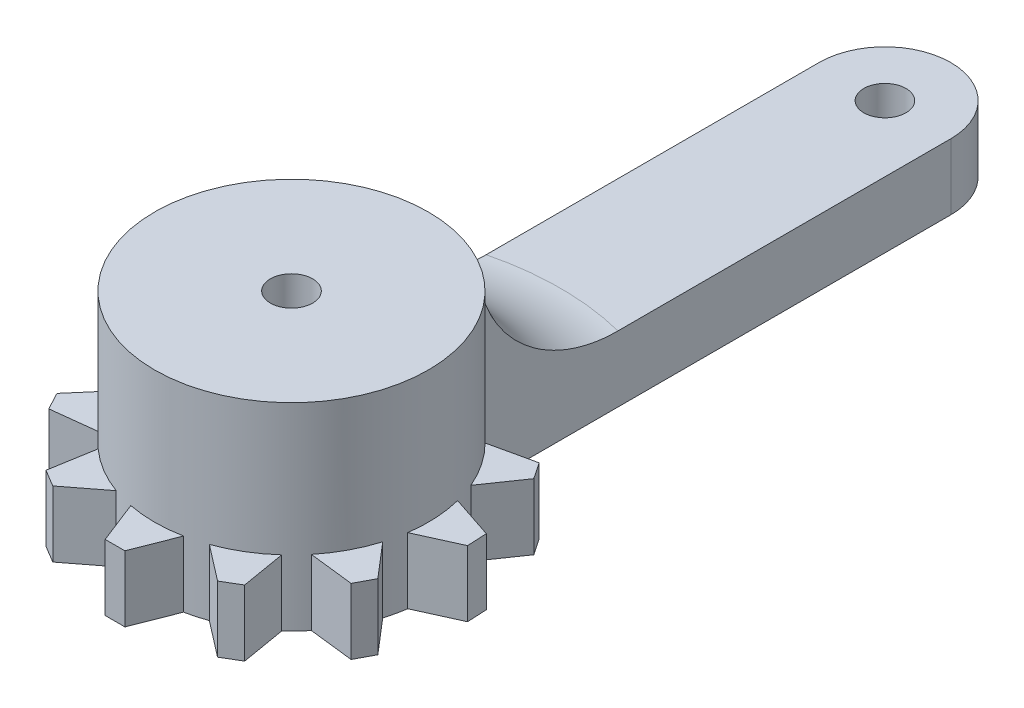
SolidWorks part; units mm, degrees
ref_plane "Front Plane" through (0, 0, 0) normal (0, 0, 1) x (1, 0, 0)
ref_plane "Top Plane" through (0, 0, 0) normal (0, 1, 0) x (1, 0, 0)
ref_plane "Right Plane" through (0, 0, 0) normal (1, 0, 0) x (0, 0, -1)
sketch "Sketch1" plane through (0, 0, 0) normal (0, 1, 0) x (1, 0, 0)
  line L0 (0, 0) -> (0, 45) construction
  line L1 (-5, 0) -> (-5, 45)
  line L2 (5, 0) -> (5, 45)
  circle A0 centre (0, 0) radius 10.38
  arc A1 (-5, 0) -> (5, 0) centre (0, 0) ccw
  arc A2 (5, 45) -> (-5, 45) centre (0, 45) ccw
  circle A3 centre (0, 45) radius 1.6
  circle A4 centre (0, 0) radius 1.6
  point P3 (0, 22.5)
  dimension "D1" = 20.76
  dimension "D4" = 3.2
  dimension "D5" = 3.2
  dimension "D2" = 10
  dimension "D3" = 45
extrude "Boss-Extrude1" add sketch "Sketch1" along normal blind 5 contours L2 A2 L1 A0 A3 | A1 L1 A0 L2 | A4 A0 L1 A1 L2 region at (0, 0, 5.2847) region at (0, 0, -3.1615) region at (0, 0, -29.1318)
sketch "Sketch2" plane through (0, 5, 0) normal (0, 1, 0) x (1, 0, 0)
  line L0 (0, -10.38) -> (0, -13.38) construction
  line L1 (-0.75, -13.38) -> (0.75, -13.38)
  line L2 (0.75, -13.38) -> (2, -10.1855)
  line L3 (-0.75, -13.38) -> (-2, -10.1855)
  arc A0 (-5, 9.0964) -> (5, 9.0964) centre (0, 0) ccw construction
  arc A1 (-2, -10.1855) -> (2, -10.1855) centre (0, 0) ccw
  point P14 (0, -13.38)
  dimension "D1" = 3
  dimension "D2" = 1.5
  dimension "D3" = 4
extrude "Boss-Extrude2" add sketch "Sketch2" against normal up to surface (5 mm away) up to face at (0, 0, -23.4291)
pattern_circular "CirPattern1" count 5 every 31 about axis through (0, 5, 0) along (0, -1, 0) of "Boss-Extrude2" other way count 5
sketch "Sketch3" plane through (0, 5, 0) normal (0, 1, 0) x (1, 0, 0)
  circle A0 centre (0, 0) radius 5.975
  circle A1 centre (0, 0) radius 1.6
  circle A2 centre (0, 0) radius 3.25
  arc A3 (7.3258, 7.3537) -> (5, 9.0964) centre (0, 0) ccw construction
  dimension "D1" = 11.95
  dimension "D2" = 6.5
  dimension "D3" = 3.2
extrude "Boss-Extrude3" [suppressed] add sketch "Sketch3" along normal blind 6.6 contours A0 A2
chamfer "Chamfer1" [suppressed] distance 1 angle 45
chamfer "Chamfer2" [suppressed] distance 0.5 angle 45
sketch "Sketch4" plane through (0, 5, 0) normal (0, 1, 0) x (1, 0, 0)
  circle A0 centre (0, 0) radius 10.38
  circle A1 centre (0, 0) radius 1.6
  circle A2 centre (0, 0) radius 1.6 construction
  arc A3 (-10.2762, -1.4642) -> (-9.9322, -3.0159) centre (0, 0) ccw construction
extrude "Boss-Extrude4" add sketch "Sketch4" along normal blind 10
fillet "Fillet1" radius 10 1 edges at (0, 5, -10.38)
